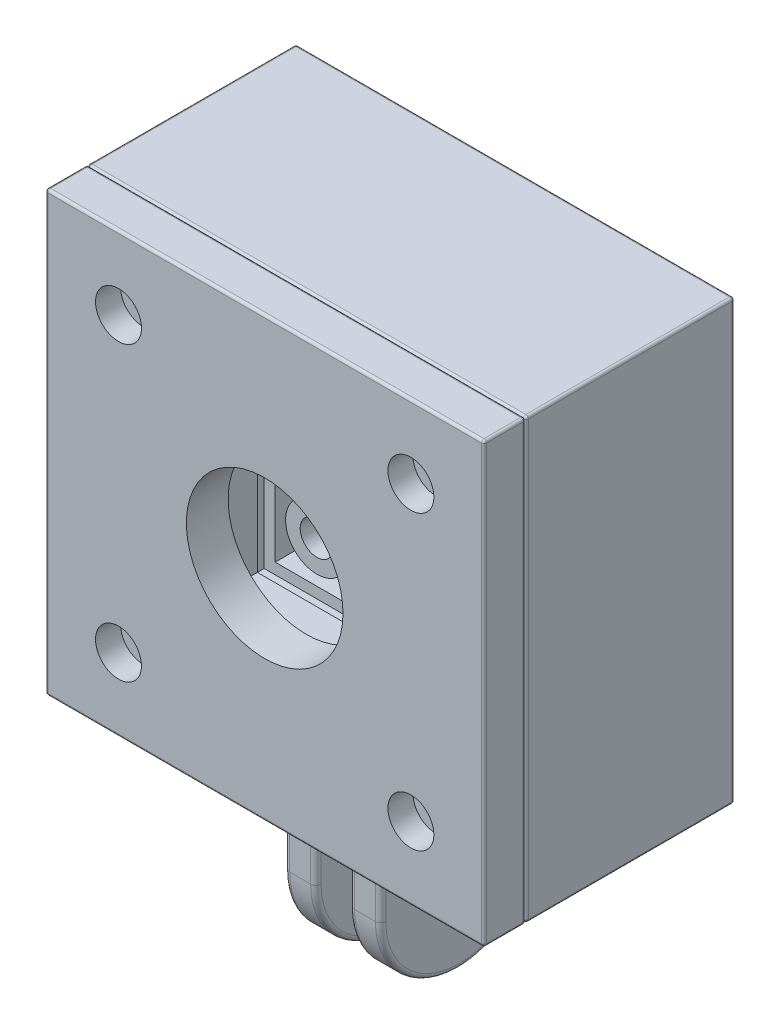
SolidWorks part; units mm, degrees
ref_plane "Ebene vorne" through (0, 0, 0) normal (0, 0, 1) x (1, 0, 0)
ref_plane "Ebene oben" through (0, 0, 0) normal (0, 1, 0) x (1, 0, 0)
ref_plane "Ebene rechts" through (0, 0, 0) normal (1, 0, 0) x (0, 0, -1)
sketch "Skizze1" plane through (0, 0, 0) normal (0, 0, 1) x (1, 0, 0)
  line L1 (-21, -21) -> (21, -21)
  line L2 (-21, -21) -> (-21, 21)
  line L3 (-21, 21) -> (21, 21)
  line L4 (21, -21) -> (21, 21)
  line L7 (-14, -14) -> (14, -14) construction
  line L8 (-14, -14) -> (-14, 14) construction
  line L9 (-14, 14) -> (14, 14) construction
  line L10 (14, -14) -> (14, 14) construction
  line L11 (-14, -14) -> (14, 14) construction
  line L12 (-14, 14) -> (14, -14) construction
  line L13 (-21, -21) -> (21, -21)
  line L14 (-21, -21) -> (-21, 21)
  line L15 (-21, 21) -> (21, 21)
  line L16 (21, -21) -> (21, 21)
  line L17 (-21, -21) -> (21, 21) construction
  line L18 (-21, 21) -> (21, -21) construction
  line L19 (-19.05, -19.05) -> (19.05, -19.05)
  line L20 (-19.05, -19.05) -> (-19.05, 19.05)
  line L21 (-19.05, 19.05) -> (19.05, 19.05)
  line L22 (19.05, -19.05) -> (19.05, 19.05)
  line L23 (-19.05, -19.05) -> (19.05, 19.05) construction
  line L24 (-19.05, 19.05) -> (19.05, -19.05) construction
  point P0 (0, 0)
  point P5 (0, 0)
  point P11 (0, 0)
  point P12 (0, 0)
  dimension "D1" = 42
  dimension "D2" = 28
  dimension "D3" = 38.1
extrude "Aufsatz-Linear austragen1" add sketch "Skizze1" along normal blind 2.5 contours L4 L1 L2 L3
sketch "Skizze2" plane through (0, 0, 2.5) normal (0, 0, 1) x (1, 0, 0)
  line L1 (-19.05, -19.05) -> (19.05, -19.05)
  line L2 (-19.05, -19.05) -> (-19.05, 19.05)
  line L3 (-19.05, 19.05) -> (19.05, 19.05)
  line L4 (19.05, -19.05) -> (19.05, 19.05)
  line L5 (-19.05, -19.05) -> (19.05, 19.05) construction
  line L6 (-19.05, 19.05) -> (19.05, -19.05) construction
  line L8 (-21, -21) -> (21, -21)
  line L9 (-21, -21) -> (-21, 21)
  line L10 (-21, 21) -> (21, 21)
  line L11 (21, -21) -> (21, 21)
  line L12 (-21, -21) -> (21, 21) construction
  line L13 (-21, 21) -> (21, -21) construction
  point P0 (0, 0)
extrude "Aufsatz-Linear austragen2" add sketch "Skizze2" along normal blind 17.5
sketch "Skizze3" plane through (0, 0, 2.5) normal (0, 0, 1) x (1, 0, 0)
  circle A0 centre (-14, 14) radius 3
  circle A1 centre (14, 14) radius 3
  circle A2 centre (-14, -14) radius 3
  circle A3 centre (14, -14) radius 3
  dimension "D1" = 6
  dimension "D2" = 6
  dimension "D3" = 6
  dimension "D4" = 6
extrude "Aufsatz-Linear austragen3" add sketch "Skizze3" along normal blind 2.5
hole_wizard "Ø3.2 (3.2) Durchmesser Bohrung1" positions "Skizze4" profile "Skizze5" hole size "Ø3.2" standard "DIN" end condition through all
sketch "Skizze4" plane through (0, 0, 5) normal (0, 0, 1) x (1, 0, 0)
  point P0 (-14, 14)
  point P3 (14, 14)
  point P6 (-14, -14)
  point P9 (14, -14)
sketch "Skizze5" plane through (-14, 14, 5) normal (1, 0, 0) x (0, -1, 0)
  line L0 (0, 0) -> (0, 5)
  line L1 (0, 5) -> (1.6, 5)
  line L2 (1.6, 5) -> (1.6, 0)
  line L5 (1.6, 0) -> (0, 0)
  line L11 (0, -6.35) -> (0, 107.95) construction
  dimension "Bohrerdurchmesser" = 3.2
  dimension "Bohrungstiefe" = 5
sketch "Skizze6" plane through (0, 0, 2.5) normal (0, 0, 1) x (1, 0, 0)
  line L0 (-19.05, -19.05) -> (19.05, -19.05) construction
  line L2 (10.07, -15.165) -> (10.07, -10.165)
  line L3 (10.07, -10.165) -> (0.07, -10.165)
  line L4 (0.07, -10.165) -> (0.07, -15.165)
  line L5 (0.07, -15.165) -> (10.07, -15.165)
  circle A0 centre (14, -14) radius 1.6 construction
  dimension "D1" = 3.93
  dimension "D2" = 3.885
  dimension "D3" = 5
  dimension "D4" = 10
extrude "Schnitt-Linear austragen1" cut sketch "Skizze6" against normal blind 2.5
sketch "Skizze7" plane through (0, 0, 2.5) normal (0, 0, 1) x (1, 0, 0)
  line L1 (-19.05, -19.05) -> (19.05, -19.05)
  line L2 (-19.05, -19.05) -> (-19.05, 19.05)
  line L3 (-19.05, 19.05) -> (19.05, 19.05)
  line L4 (19.05, -19.05) -> (19.05, 19.05)
  line L5 (-19.05, -19.05) -> (19.05, 19.05) construction
  line L6 (-19.05, 19.05) -> (19.05, -19.05) construction
  line L7 (-18, -18) -> (18, -18)
  line L8 (-18, -18) -> (-18, 18)
  line L9 (-18, 18) -> (18, 18)
  line L10 (18, -18) -> (18, 18)
  line L11 (-18, -18) -> (18, 18) construction
  line L12 (-18, 18) -> (18, -18) construction
  point P0 (0, 0)
  point P5 (0, 0)
  dimension "D1" = 36
extrude "Aufsatz-Linear austragen4" add sketch "Skizze7" along normal up to surface (2.5 mm away) up to face at (-12.4, 14, 5)
fillet "Verrundung1" radius 0.25 32 edges at (18, 0, 2.5) (0, 18, 2.5) (-18, 0, 2.5) (0, -18, 2.5) (5.07, -10.165, 2.5) (0.07, -12.665, 2.5) (5.07, -15.165, 2.5) (10.07, -12.665, 2.5) (5.07, -10.165, 0) (0.07, -12.665, 0) (5.07, -15.165, 0) (10.07, -12.665, 0) (-12.4, 14, 0) (15.6, 14, 0) (-12.4, -14, 0) (15.6, -14, 0) (17, -14, 2.5) (-11, -14, 2.5) (17, 14, 2.5) (-11, 14, 2.5) (21, 0, 20) (0, 21, 20) (-21, 0, 20) (0, -21, 20) (0, 21, 0) (21, 0, 0) (0, -21, 0) (-21, 0, 0) (21, 21, 10) (21, -21, 10) (-21, 21, 10) (-21, -21, 10)
sketch "Skizze8" plane through (0, 0, 20) normal (0, 0, 1) x (1, 0, 0)
  line L5 (-21, -21) -> (21, 21) construction
  line L6 (-21, 21) -> (21, -21) construction
  line L7 (21, -21) -> (-21, -21)
  line L8 (21, -21) -> (21, 21)
  line L9 (21, 21) -> (-21, 21)
  line L10 (-21, -21) -> (-21, 21)
  line L11 (21, -21) -> (-21, 21) construction
  line L12 (21, 21) -> (-21, -21) construction
  circle A0 centre (0, 0) radius 7.5
  point P0 (0, 0)
  dimension "D1" = 15
extrude "Aufsatz-Linear austragen5" add sketch "Skizze8" along normal blind 4 separate body
hole_wizard "Stirnsenkung für M2 Zylinderschraube mit Innensechskant1" positions "Skizze9" profile "Skizze10" counterbore size "M2" standard "DIN"
sketch "Skizze9" plane through (0, 0, 24) normal (0, 0, 1) x (1, 0, 0)
  point P0 (-14, 14)
  point P3 (14, 14)
  point P6 (-14, -14)
  point P9 (14, -14)
sketch "Skizze10" plane through (-14, 14, 24) normal (1, 0, 0) x (0, -1, 0)
  line L0 (0, 0) -> (0, 10.721)
  line L1 (0, 10.721) -> (1.2, 10)
  line L2 (1.2, 10) -> (1.2, 2.4)
  line L3 (1.2, 2.4) -> (2.2, 2.4)
  line L4 (2.2, 2.4) -> (2.2, 0)
  line L5 (2.2, 0) -> (0, 0)
  line L10 (0, 10.721) -> (-1.2, 10) construction
  line L11 (0, -6.35) -> (0, 107.95) construction
  dimension "Bohrerdurchmesser" = 2.4
  dimension "Bohrungstiefe" = 10
  dimension "Senkdurchmesser2" = 4.4
  dimension "Senktiefe2" = 2.4
  dimension "Spitzenwinkel" = 118
sketch "Skizze11" plane through (0, 0, 20) normal (0, 0, -1) x (-1, 0, 0)
  line L1 (-19.05, -19.05) -> (19.05, -19.05)
  line L2 (-19.05, -19.05) -> (-19.05, 19.05)
  line L3 (-19.05, 19.05) -> (19.05, 19.05)
  line L4 (19.05, -19.05) -> (19.05, 19.05)
  line L5 (-19.05, -19.05) -> (19.05, 19.05) construction
  line L6 (-19.05, 19.05) -> (19.05, -19.05) construction
  line L7 (-18, -18) -> (18, -18)
  line L8 (-18, -18) -> (-18, 18)
  line L9 (-18, 18) -> (18, 18)
  line L10 (18, -18) -> (18, 18)
  line L11 (-18, -18) -> (18, 18) construction
  line L12 (-18, 18) -> (18, -18) construction
  point P0 (0, 0)
  point P5 (0, 0)
  dimension "D1" = 38.1
  dimension "D2" = 36
extrude "Aufsatz-Linear austragen6" add sketch "Skizze11" along normal blind 13.3
fillet "Verrundung2" radius 0.25 12 edges at (-21, 0, 20) (-21, 21, 22) (0, 21, 20) (21, 0, 20) (0, -21, 20) (-21, -21, 22) (-21, 0, 24) (0, 21, 24) (21, 21, 22) (21, -21, 22) (0, -21, 24) (21, 0, 24)
ref_plane "Ebene1" through (0, -21, 0) normal (0, -1, 0) x (-1, 0, 0)
sketch "Skizze12" plane through (0, -21, 0) normal (0, -1, 0) x (1, 0, 0)
  line L0 (0, 0) -> (0, 9.0954) construction
  line L1 (-20.75, 10) -> (49979.25, 10) construction
  line L2 (-20.75, 19.75) -> (-20.75, 0.25) construction
  line L3 (-4.6, 17.5) -> (-1.6, 17.5)
  line L4 (-4.6, 17.5) -> (-4.6, 2.5)
  line L5 (-4.6, 2.5) -> (-1.6, 2.5)
  line L6 (4.6, 17.5) -> (4.6, 2.5)
  line L8 (-1.6, 17.5) -> (-1.6, 2.5)
  line L9 (1.6, 17.5) -> (1.6, 2.5)
  line L10 (1.6, 17.5) -> (4.6, 17.5)
  line L11 (1.6, 2.5) -> (4.6, 2.5)
  line L12 (21, 19.75) -> (21, 0.25) construction
  point P7 (-20.75, 10)
  dimension "D1" = 3
  dimension "D2" = 21
  dimension "D3" = 3
  dimension "D4" = 15
  dimension "D5" = 3.2
  dimension "D6" = 7.5
  dimension "D7" = 1.6
extrude "Aufsatz-Linear austragen7" add sketch "Skizze12" along normal blind 17
fillet "Verrundung3" radius 7.5 4 edges at (3.1, -38, 17.5) (3.1, -38, 2.5) (-3.1, -38, 2.5) (-3.1, -38, 17.5)
sketch "Skizze13" plane through (-4.6, 0, 0) normal (-1, 0, 0) x (0, 0, 1)
  line L0 (2.5, -30.5) -> (17.5, -30.5) construction
  circle A0 centre (10, -30.5) radius 2.75
  dimension "D1" = 5.5
extrude "Schnitt-Linear austragen2" cut sketch "Skizze13" against normal through all
fillet "Verrundung4" radius 2 6 edges at (4.6, -21, 10) (3.1, -21, 17.5) (3.1, -21, 2.5) (-3.1, -21, 2.5) (-3.1, -21, 17.5) (-4.6, -21, 10)
fillet "Verrundung5" radius 1.5 2 edges at (1.6, -21, 10) (-1.6, -21, 10)
fillet "Verrundung6" radius 0.5 28 edges at (1.3553, -21.6788, 2.0015) (1.6, -22.748, 2.4841) (1.6, -26.75, 2.5) (1.6, -35.8033, 4.6967) (1.3553, -21.6788, 17.9985) (1.6, -22.748, 17.5159) (1.6, -26.75, 17.5) (5.1858, -21.5858, 18.0858) (4.6, -26.75, 17.5) (5.1858, -21.5858, 1.9142) (4.6, -26.75, 2.5) (4.6, -35.8033, 4.6967) (-5.1858, -21.5858, 1.9142) (-4.6, -26.75, 2.5) (-4.6, -35.8033, 4.6967) (-5.1858, -21.5858, 18.0858) (-4.6, -26.75, 17.5) (-1.3553, -21.6788, 17.9985) (-1.6, -22.748, 17.5159) (-1.6, -26.75, 17.5) (-1.3553, -21.6788, 2.0015) (-1.6, -22.748, 2.4841) (-1.6, -26.75, 2.5) (-1.6, -35.8033, 4.6967) (1.6, -35.8033, 15.3033) (4.6, -35.8033, 15.3033) (-4.6, -35.8033, 15.3033) (-1.6, -35.8033, 15.3033)
